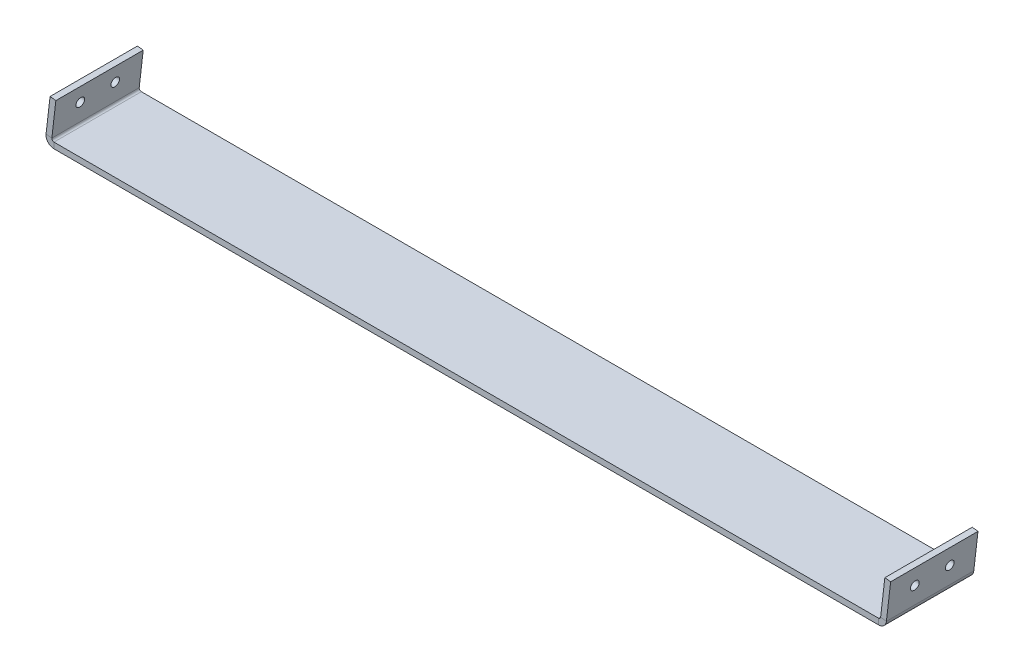
SolidWorks part; units mm, degrees
note: The reader was unsure of these and kept them because the rebuilt part matched: flange length of "Edge-Flange1", "Edge-Flange2".
material "6061 Alloy"
ref_plane "Front Plane" through (0, 0, 0) normal (0, 0, 1) x (1, 0, 0)
ref_plane "Top Plane" through (0, 0, 0) normal (0, 1, 0) x (1, 0, 0)
ref_plane "Right Plane" through (0, 0, 0) normal (1, 0, 0) x (0, 0, -1)
sketch "Sketch1" plane through (0, 0, 0) normal (0, 1, 0) x (1, 0, 0)
  line L1 (0, 0) -> (284.5815, 0)
  line L2 (0, 0) -> (0, -30)
  line L3 (0, -30) -> (284.5815, -30)
  line L4 (284.5815, 0) -> (284.5815, -30)
  dimension "D1" = 30
  dimension "D2" = 284.5815
sheet metal parameters "Sheet-Metal1" thickness 2 parameters "D1"=0.7366
base flange "Base-Flange1" sketch "Sketch1" thickness 2 reverse thickness direction no parameters "D1"=0.7366
edge flange "Edge-Flange1" sketch "Sketch6" flange angle 83.396 flange length 15 flange position material outside bend radius 0.7366 thickness 2 relief rectangular parameters "D6"=10
sketch "Sketch6" plane through (0, 0, 0) normal (-0.9934, 0.115, 0) x (0, 0, 1)
  line L2 (0, 0) -> (0, 12.7551)
  line L3 (0, 12.7551) -> (30, 12.7551)
  line L4 (30, 12.7551) -> (30, 0)
  line L5 (0, 0) -> (30, 0) construction
  line L6 (0, 0) -> (30, 0)
bend "EdgeBend1" bend radius 0.7366 bend angle 96.604 parameters "D5"=1
edge flange "Edge-Flange2" sketch "Sketch9" flange angle 96.604 flange length 15 flange position material outside bend radius 0.7366 thickness 2 relief rectangular parameters "D6"=10
sketch "Sketch9" plane through (284.5815, 0, 0) normal (0.9934, -0.115, 0) x (0, 0, -1)
  line L0 (-30, 0) -> (0, 0) construction
  line L1 (-30, 0) -> (0, 0)
  line L2 (-30, 0) -> (-30, 13.2182)
  line L3 (-30, 13.2182) -> (0, 13.2182)
  line L4 (0, 13.2182) -> (0, 0)
bend "EdgeBend2" bend radius 0.7366 bend angle 83.396 parameters "D5"=2
sketch "Sketch10" plane through (-1.9867, 0.23, 0) normal (-0.9934, 0.115, 0) x (0, 0, 1)
  line L0 (15, 12.7551) -> (15, -1.9098) construction
  line L1 (30, 12.7551) -> (0, 12.7551) construction
  line L2 (0, -1.9098) -> (30, -1.9098) construction
  line L3 (30, -1.8916) -> (0, -1.8916) construction
  circle A0 centre (9, 7.4084) radius 1.5
  circle A1 centre (21, 7.4084) radius 1.5
  dimension "D1" = 3
  dimension "D2" = 3
  dimension "D3" = 6
  dimension "D4" = 6
  dimension "D5" = 9.3
extrude "Mounting Holes" cut sketch "Sketch10" against normal up to surface (2 mm away) normal cut yes up to face at (0.781, 6.7459, 15)
sketch "Sketch11" plane through (282.8045, -32.7403, 0) normal (0.9934, -0.115, 0) x (0, 0, -1)
  line L0 (-15, 45.9456) -> (-15, 33.3836) construction
  line L1 (0, 45.9456) -> (-30, 45.9456) construction
  line L2 (0, 33.3836) -> (-30, 33.3836) construction
  circle A0 centre (-21, 39.9456) radius 1.5
  circle A1 centre (-9, 39.9456) radius 1.5
  dimension "D1" = 3
  dimension "D2" = 3
  dimension "D3" = 6
  dimension "D4" = 6
  dimension "D5" = 6
extrude "Cut-Extrude2" cut sketch "Sketch11" against normal up to surface (2 mm away) normal cut yes up to face at (285.3793, 6.8912, 15)
flat pattern "Flat-Pattern1" [suppressed]
sketch "Bend-Lines1" plane through (0, 0, 0) normal (0, 1, 0) x (1, 0, 0)
sketch3d "Bounding-Box1" [suppressed]
  line L0 (-275, -30, 0) -> (0, -30, 0) construction
  line L1 (-275, 0, 0) -> (0, 0, 0) construction
  line L2 (-275, -30, 0) -> (-275, 0, 0) construction
  line L3 (0, -30, 0) -> (0, 0, 0) construction
bend of the flat pattern "Flatten-<EdgeBend1>1"
bend of the flat pattern "Flatten-<EdgeBend2>1"
equation "\"D4@Sketch10\"=\"D3@Sketch10\""
equation "\"D5@Sketch11\"=\"D4@Sketch11\""
